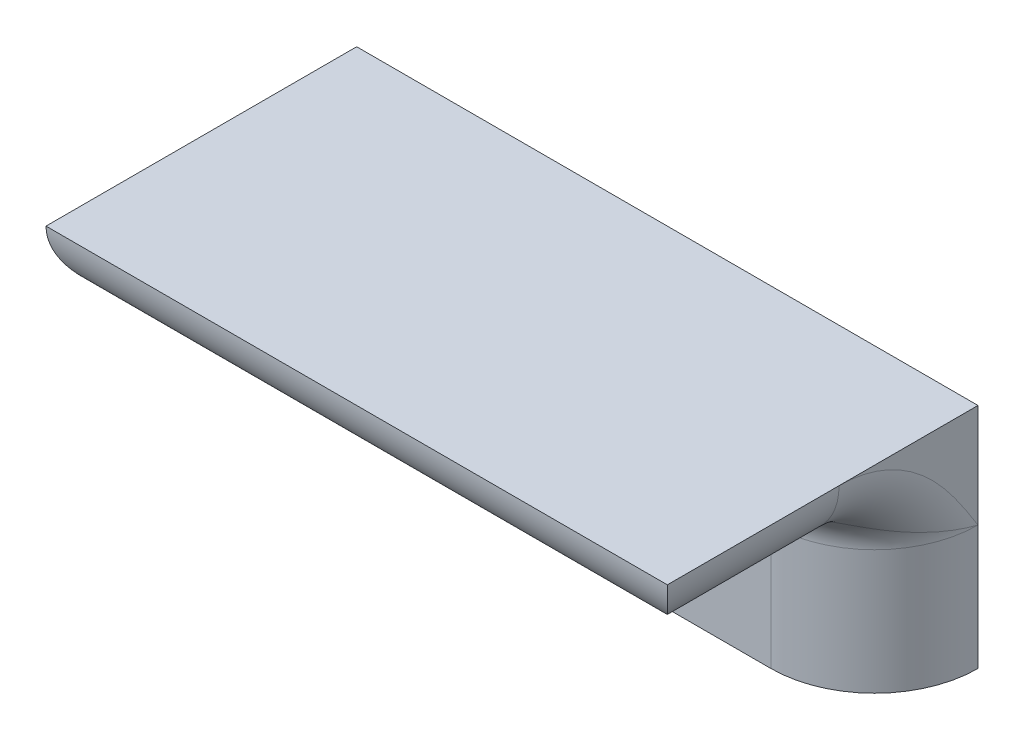
SolidWorks part; units mm, degrees
ref_plane "Front Plane" through (0, 0, 0) normal (0, 0, 1) x (1, 0, 0)
ref_plane "Top Plane" through (0, 0, 0) normal (0, 1, 0) x (1, 0, 0)
ref_plane "Right Plane" through (0, 0, 0) normal (1, 0, 0) x (0, 0, -1)
sketch "Sketch1" plane through (0, 0, 0) normal (0, 1, 0) x (1, 0, 0)
  line L1 (0, 0) -> (30, 0)
  line L2 (0, 0) -> (0, 5)
  line L3 (0, 5) -> (30, 5)
  line L4 (30, 0) -> (30, 5)
  dimension "D1" = 5
  dimension "D2" = 30
extrude "Boss-Extrude1" add sketch "Sketch1" along normal blind 8
sketch "Sketch2" plane through (0, 8, 0) normal (0, 1, 0) x (1, 0, 0)
  line L1 (0, 5) -> (30, 5)
  line L2 (0, 5) -> (0, -10)
  line L3 (0, -10) -> (30, -10)
  line L4 (30, 5) -> (30, -10)
  dimension "D1" = 15
extrude "Boss-Extrude2" add sketch "Sketch2" along normal blind 3
fillet "Fillet1" radius 5 2 edges at (0, 4, 0) (30, 4, 0)
fillet "Fillet2" radius 2 3 edges at (1.4645, 8, -1.4645) (28.5355, 8, -1.4645) (15, 8, 0)
fillet "Fillet3" radius 3 5 edges at (0, 7.734, -1.6773) (30, 7.734, -1.6773) (0, 8, 4.9495) (30, 8, 4.9495) (15, 8, 10)
